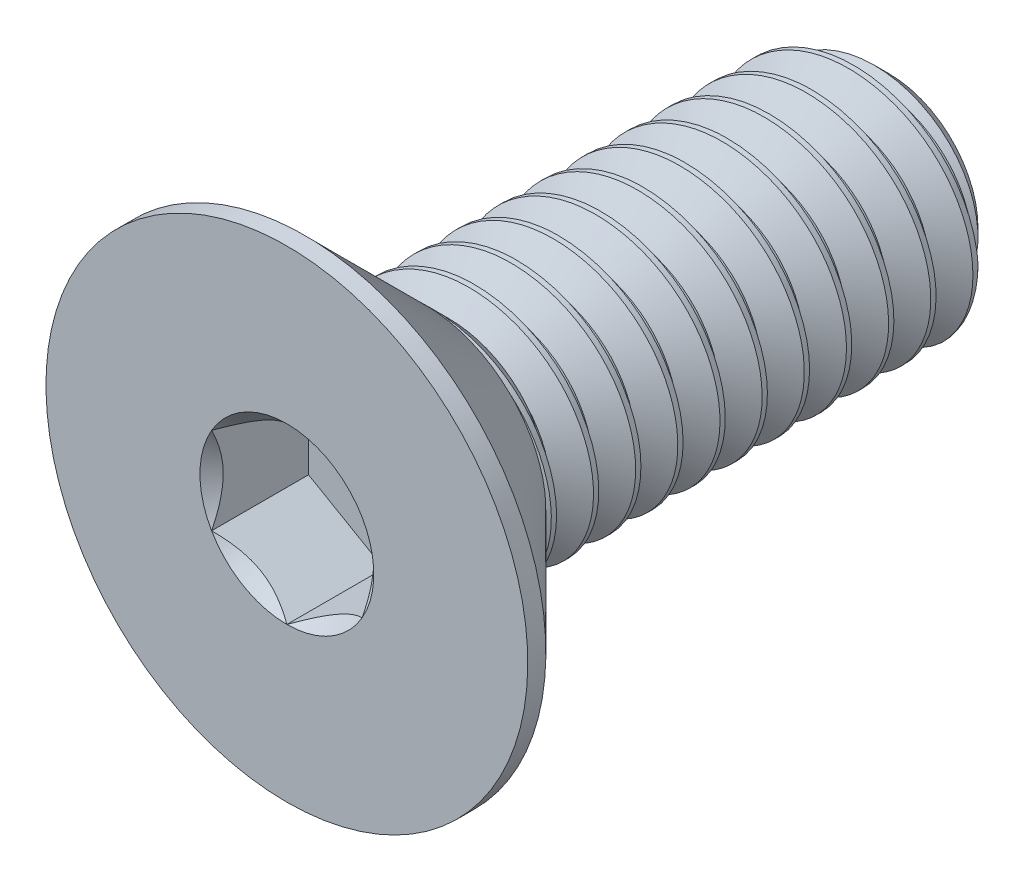
SolidWorks part; units mm, degrees
ref_plane "Front" through (0, 0, 0) normal (0, 0, 1) x (1, 0, 0)
ref_plane "Top" through (0, 0, 0) normal (0, 1, 0) x (1, 0, 0)
ref_plane "Right" through (0, 0, 0) normal (1, 0, 0) x (0, 0, -1)
sketch "Sketch1" plane through (0, 0, 0) normal (1, 0, 0) x (0, 0, -1)
  line L0 (0, 4) -> (0.3, 4) construction
  line L1 (0.3, 4) -> (2.3, 2) construction
  line L2 (0, 2) -> (10, 2)
  line L3 (10, 2) -> (10, 0)
  line L4 (10, 0) -> (0, 0)
  line L5 (0, 0) -> (0, 4) construction
  line L6 (0, 4) -> (0, -4) construction
  line L7 (10, 2) -> (10, -2) construction
  line L8 (0, -4) -> (0.3, -4) construction
  line L9 (0.3, -4) -> (2.3, -2) construction
  line L11 (0, 2) -> (0, 0)
  line L12 (2.3, 2) -> (2.3, 0) construction
revolve "Revolve1" add sketch "Sketch1" angle 360 mid plane about L4
sketch "Sketch3" plane through (0, 0, -10) normal (0, 0, -1) x (-1, 0, 0)
  circle A0 centre (0, 0) radius 2
curve "Helix/Spiral1" pitch 0.7 height 10 radius 2 centre (0, 0, -10) axis (0, 0, 1) start towards (0, 1, 0)
sketch "Sketch2" plane through (0, 0, 0) normal (1, 0, 0) x (0, 0, -1)
  line L0 (10, 2) -> (10.6125, 2)
  line L1 (10.6125, 2) -> (10.35, 1.5453)
  line L2 (10.35, 1.5453) -> (10.2625, 1.5453)
  line L3 (10.2625, 1.5453) -> (10, 2)
  line L4 (10.1312, 1.7727) -> (10.4813, 1.7727) construction
  dimension "D1" = 60
  dimension "D2" = 0.0875
  dimension "D3" = 0.35
chamfer "Chamfer1" distance 0.525 angle 45 1 edges at (0, 2, -10)
sweep "Cut-Sweep1" cut profiles "Sketch2" path "Helix/Spiral1" align with end faces yes
sketch "Sketch7" plane through (0, 0, 0) normal (1, 0, 0) x (0, 0, -1)
  line L0 (0, 4) -> (0.3, 4) construction
  line L1 (0.3, 4) -> (2.3, 2) construction
  line L2 (0, 4) -> (0.3, 4)
  line L3 (0.3, 4) -> (2.3, 2)
  line L4 (2.3, 2) -> (2.3, 0) construction
  line L5 (2.3, 2) -> (2.3, 0)
  line L7 (0, 0) -> (0, 4) construction
  line L8 (0, 0) -> (0, 4)
  line L9 (0, 0) -> (2.3, 0)
  line L10 (4.4, 0) -> (-4.4, 0) construction
revolve "Revolve2" add sketch "Sketch7" angle 360 mid plane about L9
ref_plane "Plane1" through (0, 0, -2.3) normal (0, 0, 1) x (1, 0, 0)
sketch "Sketch8" plane through (0, 0, -2.3) normal (0, 0, 1) x (1, 0, 0)
  circle A0 centre (0, 0) radius 2
extrude "Boss-Extrude1" add sketch "Sketch8" against normal through all draft 45
sketch "Sketch5" plane through (0, 0, 0) normal (0, 0, 1) x (1, 0, 0)
  line L1 (1.25, -0.7217) -> (1.25, 0.7217)
  line L2 (1.25, 0.7217) -> (0, 1.4434)
  line L3 (0, 1.4434) -> (-1.25, 0.7217)
  line L4 (-1.25, 0.7217) -> (-1.25, -0.7217)
  line L5 (-1.25, -0.7217) -> (0, -1.4434)
  line L6 (0, -1.4434) -> (1.25, -0.7217)
  circle A0 centre (0, 0) radius 1.25 construction
  dimension "Hex" = 2.5
extrude "Cut-Extrude2" cut sketch "Sketch5" against normal blind 1.61
sketch "Sketch6" plane through (0, 0, 0) normal (0, 0, 1) x (1, 0, 0)
  circle A0 centre (0, 0) radius 1.4434
extrude "Cut-Extrude3" cut sketch "Sketch6" against normal blind 1.61 draft 45
sketch "Sketch9" [suppressed] plane through (0, 0, -5.5) normal (0, 0, 1) x (1, 0, 0)
  circle A1 centre (0, 0) radius 5
  circle A2 centre (0, 0) radius 5
  point P0 (0, 5)
  dimension "D1" = 0
extrude "Boss-Extrude2" [suppressed] add sketch "Sketch9" against normal offset from surface (18.5 mm away) 26 up to face at (0, 1.475, -10)
fillet "Fillet1" [suppressed] radius 0.4
sketch "Sketch10" plane through (0, 0, 0) normal (1, 0, 0) x (0, 0, -1)
  line L0 (10, 2) -> (10, -2) construction
  point P0 (8.95, -2)
  dimension "D1" = 1.05
equation "\"D3@Helix/Spiral1\" = \"Lg@Sketch1\""
equation "\"D2@Sketch2\" = \"D4@Helix/Spiral1\" * .125"
equation "\"D3@Sketch2\" = \"D4@Helix/Spiral1\" * .5"
equation "\"D1@Chamfer1\" = \"D4@Helix/Spiral1\" * .75"
equation "\"D1@Cut-Extrude2\" = \"Head Ht@Sketch1\" * .7"
equation "\"D1@Sketch10\" = \"D4@Helix/Spiral1\" * 1.5"
equation "\"D1@Cut-Extrude3\" = \"D1@Cut-Extrude2\""
equation "\"D1@Fillet1\" = \"Dia@Sketch1\" * .1"
